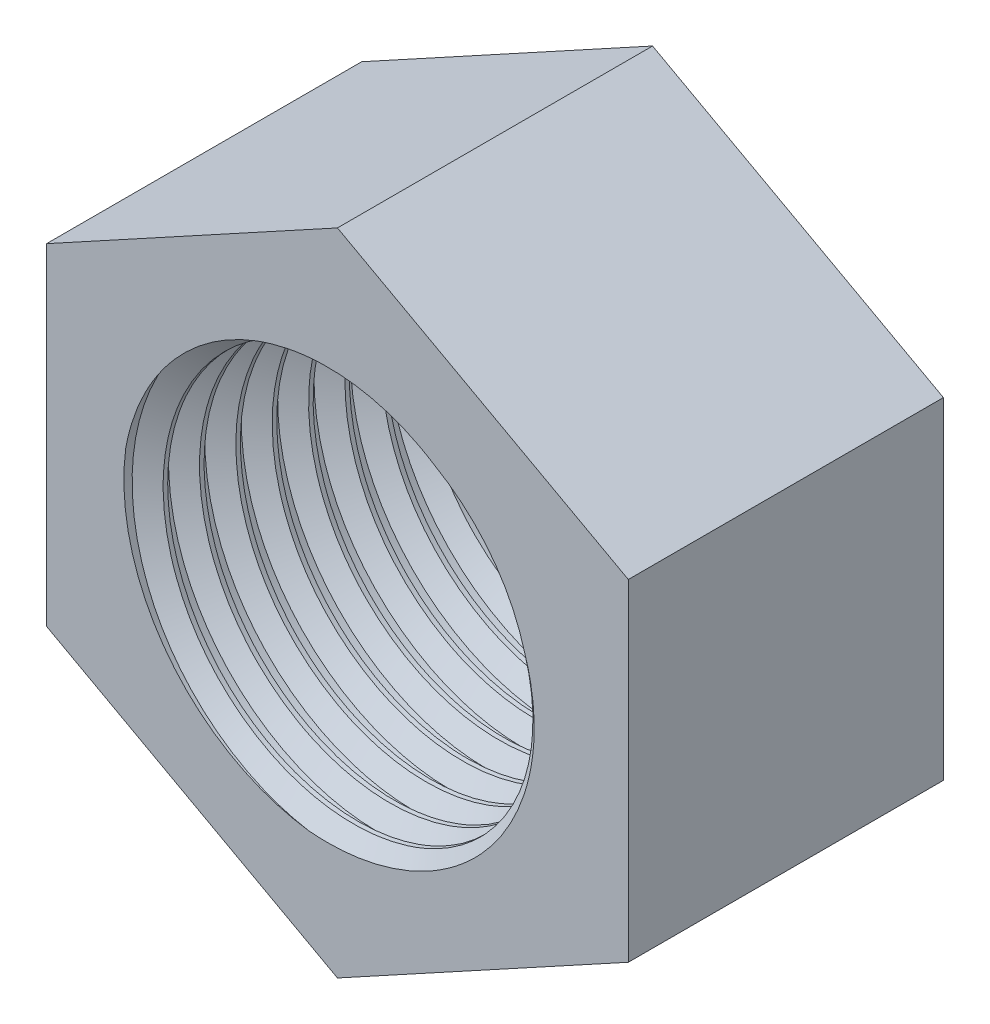
SolidWorks part; units mm, degrees
material "Gray Cast Iron"
ref_plane "Front Plane" through (0, 0, 0) normal (0, 0, 1) x (1, 0, 0)
ref_plane "Top Plane" through (0, 0, 0) normal (0, 1, 0) x (1, 0, 0)
ref_plane "Right Plane" through (0, 0, 0) normal (1, 0, 0) x (0, 0, -1)
sketch "Sketch1" plane through (0, 0, 0) normal (0, 0, 1) x (1, 0, 0)
  line L0 (0, 0) -> (-13708.9085, 0) construction
  line L1 (0, -13.4) -> (12, -6.8384)
  line L2 (12, -6.8384) -> (12, 6.8384)
  line L3 (12, 6.8384) -> (0, 13.4)
  line L4 (0, 13.4) -> (-12, 6.8384)
  line L5 (-12, 6.8384) -> (-12, -6.8384)
  line L6 (-12, -6.8384) -> (0, -13.4)
  line L7 (0, 0) -> (0, -13708.9085) construction
  circle A0 centre (0, 0) radius 8
  dimension "D3" = 16
  dimension "D1" = 24
  dimension "D2" = 26.8
extrude "Boss-Extrude1" add sketch "Sketch1" along normal blind 13
thread "Thread1" pitch 1.5 method cut profile "Thread Profile1" start angle 0, offset 5, length 28, pitch 1.5, diameter 16
ref_plane "Plane1" through (-8, 0, 18) normal (0, 1, 0) x (1, 0, 0)
sketch "Thread Profile1" plane through (-8, 0, 18) normal (0, 1, 0) x (1, 0, 0)
  line L0 (0, 0) -> (0, 1.5) construction
  line L11 (0, 0) -> (0, 1.3125)
  line L12 (0, 1.3125) -> (-0.8119, 0.8437)
  line L13 (-0.8119, 0.8437) -> (-0.8119, 0.4687)
  line L15 (-0.8119, 0.4687) -> (0, 0)
  line L17 (-0.8119, 0.6562) -> (0, 0.6562) construction
  point P2 (0, 0)
  dimension "Pitch" = 1.5
  dimension "Profile_Angle" = 60
  dimension "Profile_Land" = 0.375
  dimension "Profile_Height" = 0.8119
